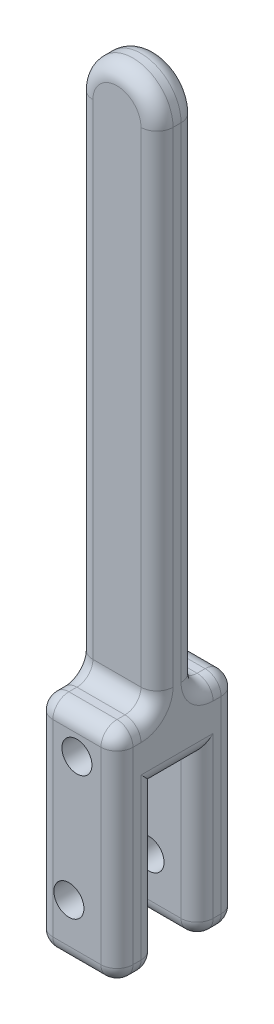
SolidWorks part; units mm, degrees
material "ABS"
ref_plane "Front Plane" through (0, 0, 0) normal (0, 0, 1) x (1, 0, 0)
ref_plane "Top Plane" through (0, 0, 0) normal (0, 1, 0) x (1, 0, 0)
ref_plane "Right Plane" through (0, 0, 0) normal (1, 0, 0) x (0, 0, -1)
sketch "Sketch1" plane through (0, 0, 0) normal (0, 0, 1) x (1, 0, 0)
  line L1 (0, 0) -> (12.7, 0)
  line L2 (0, 0) -> (0, 114.3)
  line L3 (0, 114.3) -> (12.7, 114.3)
  line L4 (12.7, 0) -> (12.7, 114.3)
  dimension "D1" = 12.7
  dimension "D2" = 114.3
extrude "Boss-Extrude1" add sketch "Sketch1" along normal blind 6.35
sketch "Sketch2" plane through (12.7, 0, 0) normal (1, 0, 0) x (0, 0, -1)
  line L0 (-6.35, 114.3) -> (0, 114.3) construction
  line L1 (-10.675, 106.8) -> (4.325, 106.8)
  line L2 (-10.675, 106.8) -> (-10.675, 121.8)
  line L3 (-10.675, 121.8) -> (4.325, 121.8)
  line L4 (4.325, 106.8) -> (4.325, 121.8)
  line L5 (-10.675, 106.8) -> (4.325, 121.8) construction
  line L6 (-10.675, 121.8) -> (4.325, 106.8) construction
  point P0 (-3.175, 114.3)
  dimension "D1" = 15
  dimension "D2" = 15
extrude "Boss-Extrude2" [suppressed] add sketch "Sketch2" along normal blind 3
draft "Draft5" [suppressed] type of draft neutral plane draft angle 45 faces to draft 1 parameters "D1"=45
fillet "Fillet1" [suppressed] radius 7.62
fillet "Fillet2" [suppressed] radius 7.62
sketch "Sketch4" plane through (0, 0, 6.35) normal (0, 0, 1) x (1, 0, 0)
  line L0 (12.7, 0) -> (12.7, 114.3) construction
  line L1 (0, 0) -> (12.7, 0)
  line L2 (0, 0) -> (0, 28.575)
  line L3 (0, 28.575) -> (12.7, 28.575)
  line L4 (12.7, 0) -> (12.7, 28.575)
  dimension "D1" = 28.575
extrude "Boss-Extrude3" add sketch "Sketch4" along normal blind 6.35
sketch "Sketch5" plane through (0, 0, 0) normal (0, 0, -1) x (-1, 0, 0)
  line L0 (0, 114.3) -> (0, 0) construction
  line L1 (-12.7, 0) -> (0, 0)
  line L2 (-12.7, 0) -> (-12.7, 28.575)
  line L3 (-12.7, 28.575) -> (0, 28.575)
  line L4 (0, 0) -> (0, 28.575)
  dimension "D1" = 28.575
extrude "Boss-Extrude4" add sketch "Sketch5" along normal blind 6.35
sketch "Sketch7" plane through (0, 0, 0) normal (-1, 0, 0) x (0, 0, 1)
  line L1 (0, 0) -> (6.35, 0)
  line L2 (0, 0) -> (0, 19.05)
  line L3 (0, 19.05) -> (6.35, 19.05)
  line L4 (6.35, 0) -> (6.35, 19.05)
  dimension "D1" = 19.05
extrude "Cut-Extrude2" cut sketch "Sketch7" against normal blind 32.512
sketch "Sketch8" plane through (0, 0, 6.35) normal (0, 0, 1) x (1, 0, 0)
  line L1 (12.7, 0) -> (0, 0) construction
  circle A0 centre (6.35, 22.86) radius 2.3813
  dimension "D2" = 4.7625
  dimension "D1" = 22.86
extrude "Cut-Extrude3" cut sketch "Sketch8" against normal through all both and the other way through all
fillet "Fillet5" 2 edges at (12.7, 114.3, 3.175) (0, 114.3, 3.175) type full round first side face at (12.7, 31.75, 3.175) second side face at (0, 31.75, 3.175) middle face at (6.35, 114.3, 3.175)
sketch "Sketch9" plane through (0, 0, 0) normal (0, -1, 0) x (1, 0, 0)
  line L4 (12.7, -6.35) -> (12.7, 0)
  line L6 (12.7, -6.35) -> (12.7, 0)
  line L7 (0, -6.35) -> (12.7, -6.35)
  line L11 (0, -6.35) -> (12.7, -6.35)
  line L12 (0, 12.7) -> (0, 6.35)
  line L14 (0, 12.7) -> (0, 6.35)
  line L15 (12.7, 12.7) -> (0, 12.7)
  line L19 (12.7, 12.7) -> (0, 12.7)
  line L21 (12.7, 0) -> (0, 0)
  line L24 (0, 6.35) -> (12.7, 6.35)
  line L26 (12.7, 0) -> (0, 0)
  line L27 (0, 0) -> (0, -6.35)
  line L28 (0, 0) -> (0, -6.35)
  line L29 (0, 6.35) -> (12.7, 6.35)
  line L30 (12.7, 6.35) -> (12.7, 12.7)
  line L31 (12.7, 6.35) -> (12.7, 12.7)
  dimension "D1" = 0
  dimension "D2" = 0
extrude "Boss-Extrude5" add sketch "Sketch9" along normal blind 6.35
fillet "Fillet6" radius 2.54 32 edges at (6.35, 114.3, 6.35) (6.35, 114.3, 0) (0, 11.1125, 12.7) (0, 6.35, 6.35) (0, 19.05, 3.175) (0, 6.35, 0) (0, 11.1125, -6.35) (0, 68.2625, 0) (0, 68.2625, 6.35) (0, -6.35, -3.175) (6.35, -6.35, 0) (6.35, -6.35, -6.35) (6.35, -6.35, 6.35) (0, -6.35, 9.525) (6.35, -6.35, 12.7) (0, 28.575, -3.175) (6.35, 28.575, -6.35) (6.35, 28.575, 0) (6.35, 28.575, 12.7) (0, 28.575, 9.525) (6.35, 28.575, 6.35) (12.7, 28.575, -3.175) (12.7, 11.1125, -6.35) (12.7, -6.35, -3.175) (12.7, 6.35, 0) (12.7, 19.05, 3.175) (12.7, 6.35, 6.35) (12.7, -6.35, 9.525) (12.7, 11.1125, 12.7) (12.7, 28.575, 9.525) (12.7, 68.2625, 6.35) (12.7, 68.2625, 0)
hole_wizard "3/16 (0.1875) Dowel Hole1" positions "Sketch10" profile "Sketch11" hole size "3/16" standard "ANSI Inch"
sketch "Sketch10" plane through (0, 0, 12.7) normal (0, 0, 1) x (1, 0, 0)
  line L0 (10.16, -6.35) -> (2.54, -6.35) construction
  line L1 (0, -3.81) -> (0, 26.035) construction
  point P0 (5.08, 2.54)
  dimension "D1" = 8.89
  dimension "D2" = 5.08
sketch "Sketch11" plane through (5.08, 2.54, 12.7) normal (1, 0, 0) x (0, -1, 0)
  line L0 (0, 0) -> (0, 24.7988)
  line L1 (0, 24.7988) -> (2.3812, 23.368)
  line L2 (2.3812, 23.368) -> (2.3812, 0)
  line L5 (2.3812, 0) -> (0, 0)
  line L10 (0, 24.7988) -> (-2.3813, 23.368) construction
  line L11 (0, -6.35) -> (0, 107.95) construction
  dimension "Hole Dia." = 4.7625
  dimension "Hole Depth" = 23.368
  dimension "Drill Angle" = 118
